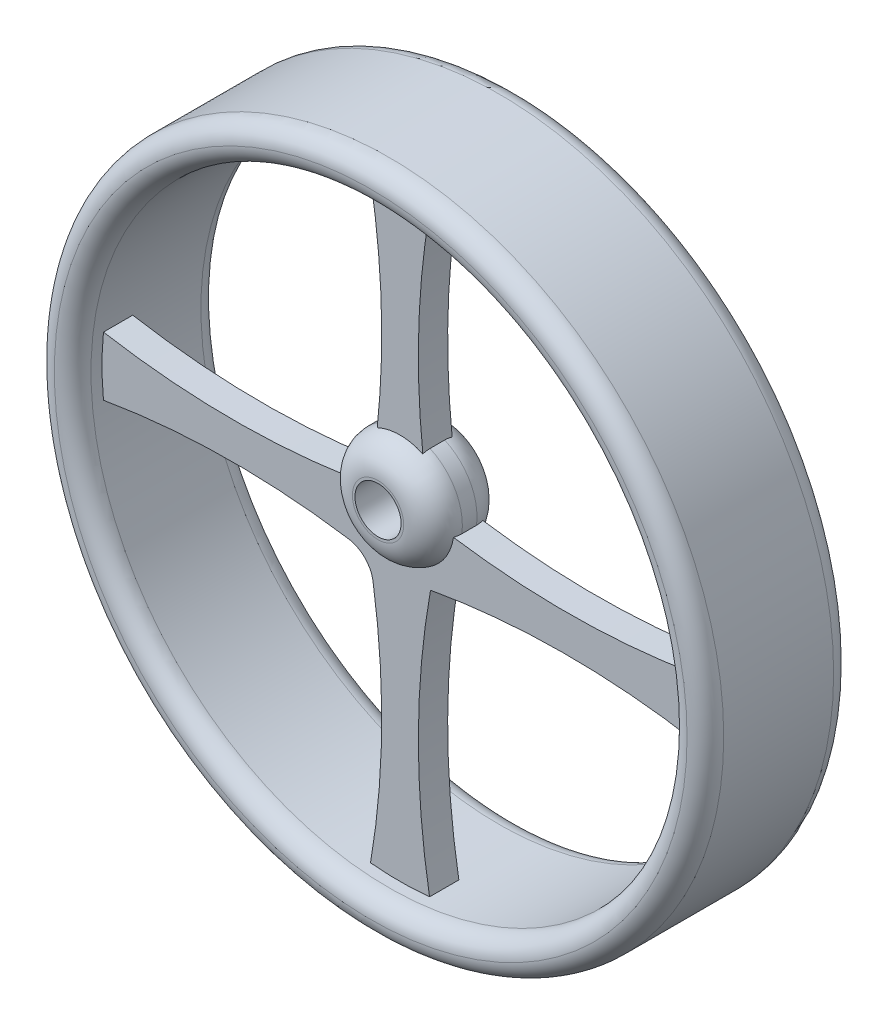
SolidWorks part; units mm, degrees
ref_plane "Front Plane" through (0, 0, 0) normal (0, 0, 1) x (1, 0, 0)
ref_plane "Top Plane" through (0, 0, 0) normal (0, 1, 0) x (1, 0, 0)
ref_plane "Right Plane" through (0, 0, 0) normal (1, 0, 0) x (0, 0, -1)
sketch "Sketch1" plane through (0, 0, 0) normal (0, 0, 1) x (1, 0, 0)
  circle A0 centre (0, 0) radius 29
  circle A3 centre (0, 0) radius 25.825
  point P22 (0, 0)
  dimension "D2" = 58
  dimension "D1" = 51.65
extrude "Boss-Extrude2" add sketch "Sketch1" along normal blind 3.81 and the other way blind 8.89
sketch "Sketch8" plane through (0, 0, 0) normal (0, 0, 1) x (1, 0, 0)
  circle A0 centre (0, 3) radius 4.7625
  dimension "D1" = 9.525
  dimension "D2" = 3
extrude "Boss-Extrude3" add sketch "Sketch8" along normal mid plane 6.35 separate body
sketch "Sketch9" plane through (0, 0, 0) normal (0, 0, 1) x (1, 0, 0)
  line L1 (3.175, 0) -> (-3.175, 0)
  line L2 (3.175, 0) -> (3.175, 28.8257) construction
  line L3 (3.175, 28.8257) -> (-3.175, 28.8257)
  line L4 (-3.175, 0) -> (-3.175, 28.8257) construction
  arc A1 (3.175, 0) -> (3.175, 28.8257) centre (67.808, 14.4128) cw
  arc A2 (-3.175, 28.8257) -> (-3.175, 0) centre (-67.808, 14.4128) cw
  circle A4 centre (0, 0) radius 29 construction
  point P8 (1.5875, 14.4128)
  point P10 (-1.5875, 14.4128)
  dimension "D1" = 6.35
  dimension "D2" = 3.175
  dimension "D3" = 3.175
  dimension "D4" = 1.5875
extrude "Boss-Extrude4" add sketch "Sketch9" along normal mid plane 2.54
ref_axis "Axis1" through (0, 0, 0) along (0, 0, 1)
pattern_circular "CirPattern1" count 4 over 360 about axis through (0, 0, 0) along (0, 0, 1) of "Boss-Extrude4"
hole_wizard "Ø3.0mm Dowel Hole2" positions "Sketch10" profile "Sketch11" hole size "Ø3.0" standard "ANSI Metric" end condition up to next
sketch "Sketch10" plane through (0, 0, 3.175) normal (0, 0, 1) x (1, 0, 0)
  point P0 (0, 3)
sketch "Sketch11" plane through (0, 3, 3.175) normal (1, 0, 0) x (0, -1, 0)
  line L0 (0, 0) -> (0, 6.35)
  line L1 (0, 6.35) -> (2, 6.35)
  line L2 (2, 6.35) -> (2, 0)
  line L5 (2, 0) -> (0, 0)
  line L11 (0, -6.35) -> (0, 107.95) construction
  dimension "Thru Hole Dia." = 4
  dimension "Thru Hole Depth" = 6.35
fillet "Fillet1" radius 1.5875 4 edges at (29, 0, -8.89) (29, 0, 3.81) (25.825, 0, -8.89) (25.825, 0, 3.81)
fillet "Fillet2" radius 2.54 3 edges at (4.7625, 3, -3.175) (4.7625, 3, 3.175) (-2.642, -2.642, 0)
equation "\"D1@Sketch1\"=\"D2@Sketch1\"-0.25"
equation "\"D2@Sketch9\"=\"D1@Sketch9\"/2"
equation "\"D4@Sketch9\"=\"D3@Sketch9\"/2"
